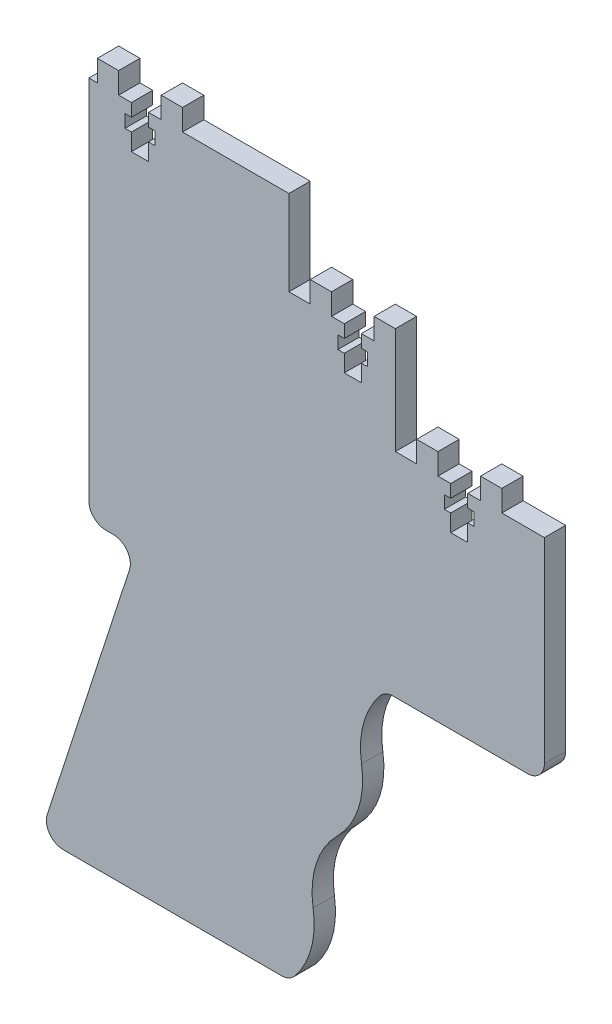
SolidWorks part; units mm, degrees
ref_plane "Plan de face" through (0, 0, 0) normal (0, 0, 1) x (1, 0, 0)
ref_plane "Plan de dessus" through (0, 0, 0) normal (0, 1, 0) x (1, 0, 0)
ref_plane "Plan de droite" through (0, 0, 0) normal (1, 0, 0) x (0, 0, -1)
sketch "Esquisse1" plane through (0, 0, 0) normal (0, 0, 1) x (1, 0, 0)
  line L0 (10, 0) -> (10, -20)
  line L1 (10, -20) -> (15, -20)
  line L2 (35, -20) -> (45, -20)
  line L3 (45, -20) -> (45, -70)
  line L4 (45, -70) -> (7.7444, -70)
  line L5 (7.7444, -70) -> (-15, -140) construction
  line L6 (-15, -140) -> (-73.4888, -140)
  line L7 (-73.4888, -140) -> (-28, 0) construction
  line L8 (-28, 0) -> (-10, 0) construction
  line L9 (-10, 0) -> (-15, 0)
  line L10 (-40, 20) -> (-15, 20)
  line L11 (-60, 20) -> (-62, 20)
  line L12 (-50.7444, -70) -> (-62, -70)
  line L13 (-50.7444, -70) -> (-73.4888, -140)
  line L14 (-15, 20) -> (-15, 0)
  line L15 (-62, -70) -> (-62, 20)
  arc A0 (7.7444, -70) -> (2.0583, -87.5) centre (22.0162, -84.311) ccw
  arc A1 (2.0583, -87.5) -> (-3.6278, -105) centre (-17.8996, -90.689) cw
  arc A2 (-3.6278, -105) -> (-9.3139, -122.5) centre (10.644, -119.311) ccw
  arc A3 (-9.3139, -122.5) -> (-15, -140) centre (-29.2718, -125.689) cw
  line B0 (28.5, -23) -> (28.5, -26)
  line B1 (23, -26) -> (23, -30)
  line B2 (27, -30) -> (27, -26)
  line B3 (28.5, -26) -> (27, -26)
  line B4 (25, -20) -> (25, -31.2208) construction
  line B5 (27, -20) -> (30, -20)
  line B6 (30, -15) -> (35, -15)
  line B7 (35, -15) -> (35, -20)
  line B8 (30, -15) -> (30, -20)
  line B9 (23, -20) -> (20, -20)
  line B10 (20, -20) -> (20, -15)
  line B11 (20, -15) -> (15, -15)
  line B12 (15, -15) -> (15, -20)
  line B13 (27, -20) -> (23, -20) construction
  line B14 (23, -20) -> (23, -23)
  line B15 (23, -26) -> (21.5, -26)
  line B16 (21.5, -23) -> (23, -23)
  line B17 (23, -30) -> (27, -30)
  line B18 (27, -23) -> (28.5, -23)
  line B19 (21.5, -26) -> (21.5, -23)
  line B20 (27, -23) -> (27, -20)
  line B21 (25, -30) -> (25, -20) construction
  line B22 (3.5, -3) -> (3.5, -6)
  line B23 (-2, -6) -> (-2, -10)
  line B24 (2, -10) -> (2, -6)
  line B25 (3.5, -6) -> (2, -6)
  line B26 (0, 0) -> (0, -11.2208) construction
  line B27 (2, 0) -> (5, 0)
  line B28 (5, 5) -> (10, 5)
  line B29 (10, 5) -> (10, 0)
  line B30 (5, 5) -> (5, 0)
  line B31 (-2, 0) -> (-5, 0)
  line B32 (-5, 0) -> (-5, 5)
  line B33 (-5, 5) -> (-10, 5)
  line B34 (-10, 5) -> (-10, 0)
  line B35 (2, 0) -> (-2, 0) construction
  line B36 (-2, 0) -> (-2, -3)
  line B37 (-2, -6) -> (-3.5, -6)
  line B38 (-3.5, -3) -> (-2, -3)
  line B39 (-2, -10) -> (2, -10)
  line B40 (2, -3) -> (3.5, -3)
  line B41 (-3.5, -6) -> (-3.5, -3)
  line B42 (2, -3) -> (2, 0)
  line B43 (0, -10) -> (0, 0) construction
  line B44 (-46.5, 17) -> (-46.5, 14)
  line B45 (-52, 14) -> (-52, 10)
  line B46 (-48, 10) -> (-48, 14)
  line B47 (-46.5, 14) -> (-48, 14)
  line B48 (-50, 20) -> (-50, 8.7792) construction
  line B49 (-48, 20) -> (-45, 20)
  line B50 (-45, 25) -> (-40, 25)
  line B51 (-40, 25) -> (-40, 20)
  line B52 (-45, 25) -> (-45, 20)
  line B53 (-52, 20) -> (-55, 20)
  line B54 (-55, 20) -> (-55, 25)
  line B55 (-55, 25) -> (-60, 25)
  line B56 (-60, 25) -> (-60, 20)
  line B57 (-48, 20) -> (-52, 20) construction
  line B58 (-52, 20) -> (-52, 17)
  line B59 (-52, 14) -> (-53.5, 14)
  line B60 (-53.5, 17) -> (-52, 17)
  line B61 (-52, 10) -> (-48, 10)
  line B62 (-48, 17) -> (-46.5, 17)
  line B63 (-53.5, 14) -> (-53.5, 17)
  line B64 (-48, 17) -> (-48, 20)
  line B65 (-50, 10) -> (-50, 20) construction
  dimension "D9" = 2
  dimension "D1" = 25
  dimension "D2" = 20
  dimension "D3" = 120
  dimension "D4" = 40
  dimension "D5" = 50
  dimension "D6" = 45
  dimension "D7" = 18
  dimension "D8" = 72
  dimension "50" = 50
  dimension "D10" = 20
  dimension "D12" = 5
sketch_block_instance "Insert M4 plots ep 5mm-1"
sketch_block "Insert M4 plots ep 5mm" parameters "D1"=10, "D2"=5, "D3"=5, "D4"=7, "D5"=4, "D6"=3, "D7"=3, "D8"=10
sketch_block_instance "Insert M4 plots ep 5mm-3"
sketch_block_instance "Insert M4 plots ep 5mm-4"
extrude "Boss.-Extru.1" add sketch "Esquisse1" along normal blind 5 contours B42 B40 B22 B25 B24 B39 B23 B37 B41 B38 B36 B31 B32 B33 B34 L8 L7 L6 L5 L4 L3 L2 B7 B6 B8 B5 B20 B18 B0 B3 B2 B17 B1 B15 B19 B16 B14 B9 B10 B11 B12 L1 L0 B29 B28 B30 B27 | A1 L5 | A3 L5 region at (-21.4704, -57.1173, 0)
fillet "Congé1" radius 4 6 edges at (-15, -140, 2.5) (7.7444, -70, 2.5) (45, -70, 2.5) (-73.4888, -140, 2.5) (-62, -70, 2.5) (-50.7444, -70, 2.5)
